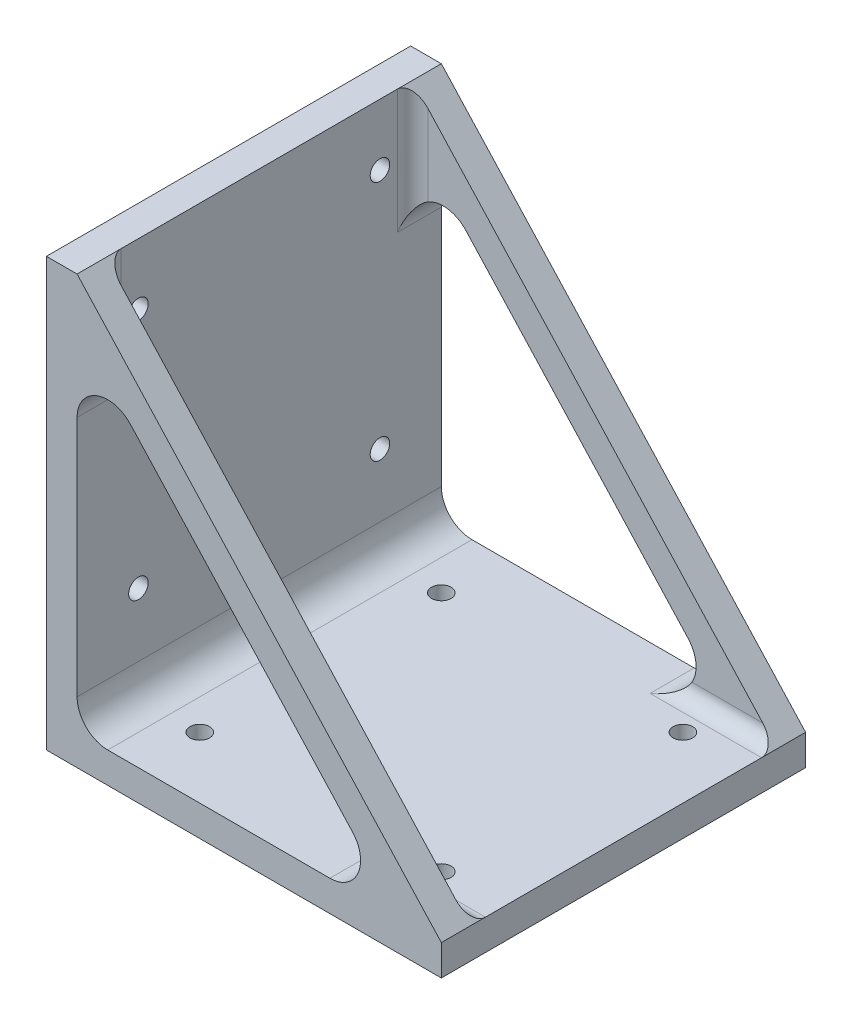
SolidWorks part; units mm, degrees
ref_plane "Front Plane" through (0, 0, 0) normal (0, 0, 1) x (1, 0, 0)
ref_plane "Top Plane" through (0, 0, 0) normal (0, 1, 0) x (1, 0, 0)
ref_plane "Right Plane" through (0, 0, 0) normal (1, 0, 0) x (0, 0, -1)
sketch "Sketch1" plane through (0, 0, 0) normal (0, 1, 0) x (1, 0, 0)
  line L1 (-25, -25) -> (25, -25) construction
  line L2 (-25, -25) -> (-25, 25) construction
  line L3 (-25, 25) -> (25, 25) construction
  line L4 (25, -25) -> (25, 25) construction
  line L5 (-25, -25) -> (25, 25) construction
  line L6 (-25, 25) -> (25, -25) construction
  line L7 (-37.7, -37.7) -> (37.7, -37.7)
  line L8 (-37.7, -37.7) -> (-37.7, 37.7)
  line L9 (-37.7, 37.7) -> (37.7, 37.7)
  line L10 (37.7, -37.7) -> (37.7, 37.7)
  line L11 (-37.7, -37.7) -> (37.7, 37.7) construction
  line L12 (-37.7, 37.7) -> (37.7, -37.7) construction
  circle A0 centre (-25, 25) radius 2.025
  circle A1 centre (25, 25) radius 2.025
  circle A2 centre (25, -25) radius 2.025
  circle A3 centre (-25, -25) radius 2.025
  point P0 (0, 0)
  point P6 (0, 0)
  point P11 (24.153, 25)
  point P13 (-25, -24.2004)
  point P17 (25.8498, -25)
  point P19 (-25.5395, 25.5395)
  dimension "D3" = 4.05
  dimension "D1" = 50
  dimension "D2" = 12.7
extrude "Boss-Extrude1" add sketch "Sketch1" against normal blind 6.35 from offset 25.4 offset against normal yes
sketch "Sketch2" plane through (-37.7, 0, 0) normal (-1, 0, 0) x (0, 0, 1)
  line L1 (-37.7, -31.75) -> (37.7, -31.75)
  line L2 (-37.7, -31.75) -> (-37.7, 56.75)
  line L3 (-37.7, 56.75) -> (37.7, 56.75)
  line L4 (37.7, -31.75) -> (37.7, 56.75)
  line L5 (37.7, -31.75) -> (37.7, -25.4) construction
  line L6 (0, 0) -> (0, 19.05) construction
  line L8 (-25, -5.95) -> (25, -5.95) construction
  line L9 (-25, -5.95) -> (-25, 44.05) construction
  line L10 (-25, 44.05) -> (25, 44.05) construction
  line L11 (25, -5.95) -> (25, 44.05) construction
  line L12 (-25, -5.95) -> (25, 44.05) construction
  line L13 (-25, 44.05) -> (25, -5.95) construction
  circle A0 centre (-25, 44.05) radius 2.025
  circle A1 centre (-25, -5.95) radius 2.025
  circle A2 centre (25, -5.95) radius 2.025
  circle A3 centre (25, 44.05) radius 2.025
  point P19 (-25, -3.5309)
  dimension "D3" = 4.05
  dimension "D1" = 50.8
  dimension "D2" = 50
extrude "Boss-Extrude2" add sketch "Sketch2" along normal blind 6.35
sketch "Sketch3" plane through (0, 0, 0) normal (0, 0, -1) x (-1, 0, 0)
  line L0 (-37.7, -25.4) -> (37.7, 56.75)
  line L1 (37.7, 56.75) -> (37.7, -25.4) construction
  line L2 (37.7, -25.4) -> (-37.7, -25.4) construction
  line L3 (-29.0808, -25.4) -> (37.7, 47.3592)
  line L4 (-37.7, -25.4) -> (-29.0808, -25.4)
  line L5 (37.7, 47.3592) -> (37.7, 56.75)
  dimension "D1" = 6.35
extrude "Boss-Extrude3" add sketch "Sketch3" along normal up to surface (37.7 mm away) from surface up to face at (-14.6833, -0.1333, -37.7) starting at face at (-14.6833, -0.1333, 37.7)
extrude "Cut-Extrude1" cut sketch "Sketch3<2>" against normal mid plane 63.5
sketch "Sketch3<2>" plane through (0, 0, 0) normal (0, 0, -1) x (-1, 0, 0) same geometry as "Sketch3"
fillet "Fillet3" radius 6.35 5 edges at (-37.7, 47.3592, 34.725) (-37.7, 47.3592, -34.725) (29.0808, -25.4, 34.725) (-37.7, -25.4, 0) (29.0808, -25.4, -34.725)
fillet "Fillet4" radius 3.175 4 edges at (-37.7, 43.8999, 31.75) (-37.7, 43.8999, -31.75) (26.1667, -25.4, -31.75) (26.1667, -25.4, 31.75)
